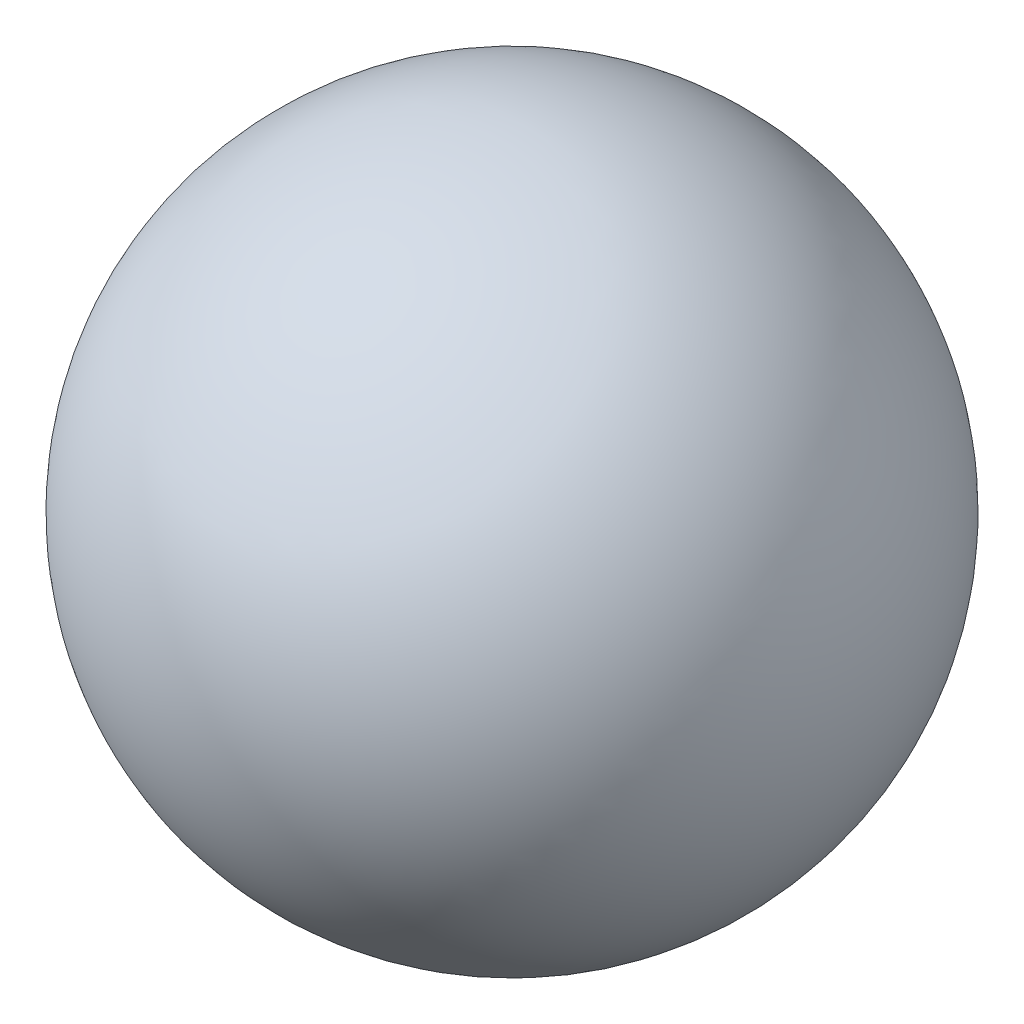
SolidWorks part; units mm, degrees
ref_plane "Front Plane" through (0, 0, 0) normal (0, 0, 1) x (1, 0, 0)
ref_plane "Top Plane" through (0, 0, 0) normal (0, 1, 0) x (1, 0, 0)
ref_plane "Right Plane" through (0, 0, 0) normal (1, 0, 0) x (0, 0, -1)
sketch "Sketch1" plane through (0, 0, 0) normal (0, 1, 0) x (1, 0, 0)
  line L0 (0, -260) -> (0, 260) construction
  line L1 (0, -140) -> (0, -260)
  line L2 (0, 140) -> (0, 260)
  circle A0 centre (0, 0) radius 140 construction
  circle A1 centre (0, 0) radius 260 construction
  arc A2 (0, 140) -> (0, -140) centre (0, 0) cw
  arc A3 (0, 260) -> (0, -260) centre (0, 0) cw
  dimension "D1" = 280
  dimension "D2" = 520
revolve "Revolve1" add sketch "Sketch1" angle 360 about L0
ref_axis "Axis1" through (0, 0, -572.1672) along (0, 0, 1)
